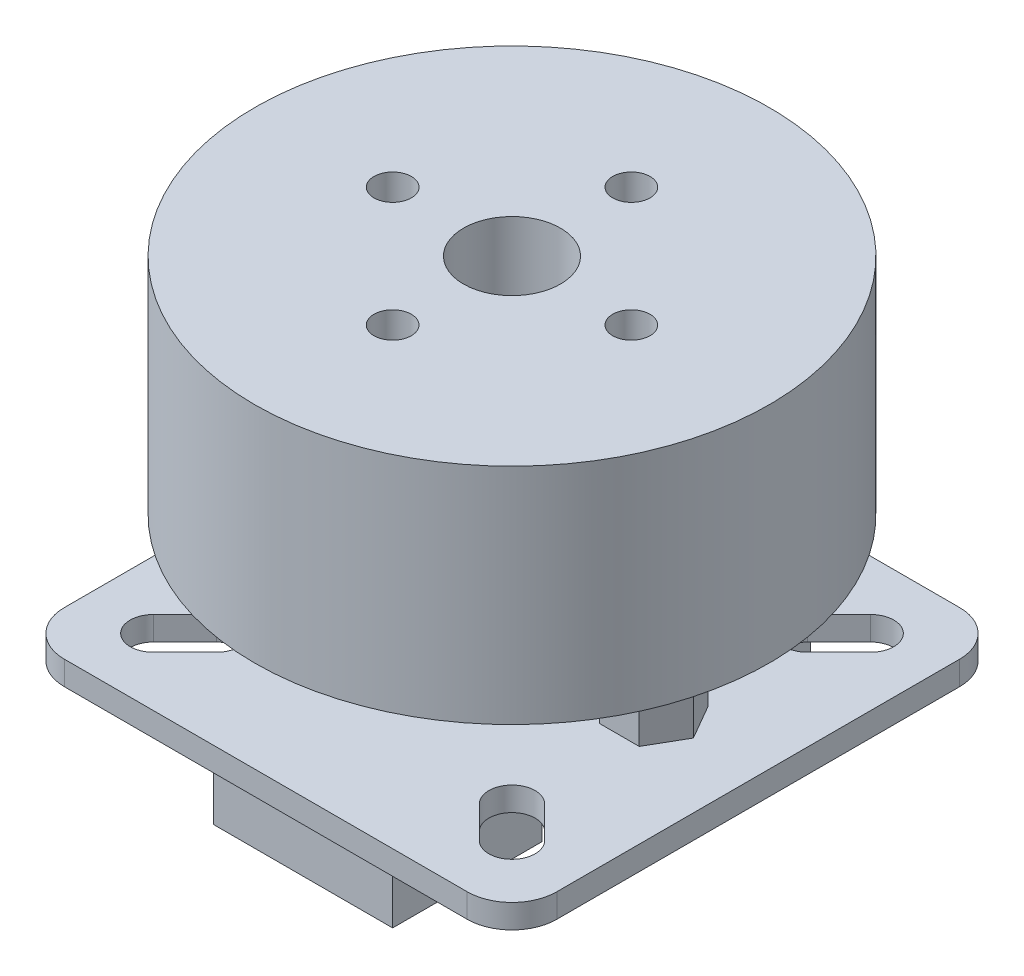
SolidWorks part; units mm, degrees
material "Cast Alloy Steel"
ref_plane "Front Plane" through (0, 0, 0) normal (0, 0, 1) x (1, 0, 0)
ref_plane "Top Plane" through (0, 0, 0) normal (0, 1, 0) x (1, 0, 0)
ref_plane "Right Plane" through (0, 0, 0) normal (1, 0, 0) x (0, 0, -1)
sketch "Sketch1" plane through (0, 0, 0) normal (0, 1, 0) x (1, 0, 0)
  circle A0 centre (0, 0) radius 17.25
  dimension "D1" = 34.5
extrude "Boss-Extrude1" add sketch "Sketch1" along normal blind 15
sketch "Sketch2" plane through (0, 0, 0) normal (0, -1, 0) x (1, 0, 0)
  circle A0 centre (0, 0) radius 6
  dimension "D1" = 12
extrude "Boss-Extrude2" add sketch "Sketch2" along normal blind 4.5
sketch "Sketch3" plane through (0, 0, 0) normal (0, -1, 0) x (1, 0, 0)
  line L1 (-6.8442, 0) -> (-8.1721, 2.3)
  line L2 (-8.1721, 2.3) -> (-10.8279, 2.3)
  line L3 (-10.8279, 2.3) -> (-12.1558, 0)
  line L4 (-12.1558, 0) -> (-10.8279, -2.3)
  line L5 (-10.8279, -2.3) -> (-8.1721, -2.3)
  line L6 (-8.1721, -2.3) -> (-6.8442, 0)
  line L7 (12.1558, 0) -> (10.8279, 2.3)
  line L8 (10.8279, 2.3) -> (8.1721, 2.3)
  line L9 (8.1721, 2.3) -> (6.8442, 0)
  line L10 (6.8442, 0) -> (8.1721, -2.3)
  line L11 (8.1721, -2.3) -> (10.8279, -2.3)
  line L12 (10.8279, -2.3) -> (12.1558, 0)
  circle A0 centre (0, 0) radius 9.5 construction
  circle A1 centre (-9.5, 0) radius 2.3 construction
  circle A2 centre (9.5, 0) radius 2.3 construction
  dimension "D1" = 19
  dimension "D2" = 4.6
  dimension "D3" = 4.6
extrude "Boss-Extrude3" add sketch "Sketch3" along normal blind 6.9
sketch "Sketch4" plane through (0, -6.9, 0) normal (0, -1, 0) x (1, 0, 0)
  line L0 (0, 21.6331) -> (0, -20.544) construction
  line L1 (-16.5, -16.5) -> (-16.5, 16.5)
  line L2 (-16.5, -16.5) -> (16.5, -16.5)
  line L3 (16.5, -16.5) -> (16.5, 16.5)
  line L4 (-16.5, 16.5) -> (16.5, 16.5)
  line L5 (24.0911, 0) -> (-31.8412, 0) construction
  line L6 (-13.1168, -10.9248) -> (-10.9955, -8.8035)
  line L7 (-10.9248, -13.1168) -> (-8.8035, -10.9955)
  line L8 (-13.1168, 10.9248) -> (-10.9955, 8.8035)
  line L9 (-10.9248, 13.1168) -> (-8.8035, 10.9955)
  line L10 (13.1168, -10.9248) -> (10.9955, -8.8035)
  line L11 (10.9248, -13.1168) -> (8.8035, -10.9955)
  line L12 (13.1168, 10.9248) -> (10.9955, 8.8035)
  line L13 (10.9248, 13.1168) -> (8.8035, 10.9955)
  circle A0 centre (0, 0) radius 17 construction
  circle A1 centre (0, 0) radius 14 construction
  circle A2 centre (0, 0) radius 9.5 construction
  circle A3 centre (0, 0) radius 8 construction
  arc A6 (-13.1168, -10.9248) -> (-10.9248, -13.1168) centre (-12.0208, -12.0208) ccw
  arc A13 (-13.1168, 10.9248) -> (-10.9248, 13.1168) centre (-12.0208, 12.0208) cw
  arc A14 (-8.8035, -10.9955) -> (-10.9955, -8.8035) centre (-9.8995, -9.8995) ccw
  arc A15 (-8.8035, 10.9955) -> (-10.9955, 8.8035) centre (-9.8995, 9.8995) cw
  arc A16 (13.1168, -10.9248) -> (10.9248, -13.1168) centre (12.0208, -12.0208) cw
  arc A17 (8.8035, -10.9955) -> (10.9955, -8.8035) centre (9.8995, -9.8995) cw
  arc A18 (8.8035, 10.9955) -> (10.9955, 8.8035) centre (9.8995, 9.8995) ccw
  arc A19 (13.1168, 10.9248) -> (10.9248, 13.1168) centre (12.0208, 12.0208) ccw
  dimension "D2" = 34
  dimension "D3" = 28
  dimension "D4" = 19
  dimension "D5" = 16
  dimension "D10" = 1.55
  dimension "D11" = 1.55
  dimension "D1" = 33
extrude "Boss-Extrude4" add sketch "Sketch4" along normal blind 1.6
fillet "Fillet1" radius 3 4 edges at (-16.5, -7.7, 16.5) (16.5, -7.7, 16.5) (16.5, -7.7, -16.5) (-16.5, -7.7, -16.5)
sketch "Sketch5" plane through (0, -8.5, 0) normal (0, -1, 0) x (1, 0, 0)
  line L0 (-23.8077, 0) -> (24.343, 0) construction
  line L1 (9.365, -12.0208) -> (10.6929, -14.3208)
  line L2 (10.6929, -14.3208) -> (13.3487, -14.3208)
  line L3 (13.3487, -14.3208) -> (14.6766, -12.0208)
  line L4 (14.6766, -12.0208) -> (13.3487, -9.7208)
  line L5 (13.3487, -9.7208) -> (10.6929, -9.7208)
  line L6 (10.6929, -9.7208) -> (9.365, -12.0208)
  line L7 (0, 21.4722) -> (0, -22.5606) construction
  line L8 (-10.6929, -9.7208) -> (-9.365, -12.0208)
  line L9 (-13.3487, -9.7208) -> (-10.6929, -9.7208)
  line L10 (-14.6766, -12.0208) -> (-13.3487, -9.7208)
  line L11 (-13.3487, -14.3208) -> (-14.6766, -12.0208)
  line L12 (-10.6929, -14.3208) -> (-13.3487, -14.3208)
  line L13 (-9.365, -12.0208) -> (-10.6929, -14.3208)
  line L14 (-13.3487, 14.3208) -> (-14.6766, 12.0208)
  line L15 (-14.6766, 12.0208) -> (-13.3487, 9.7208)
  line L16 (-13.3487, 9.7208) -> (-10.6929, 9.7208)
  line L17 (-10.6929, 9.7208) -> (-9.365, 12.0208)
  line L18 (-9.365, 12.0208) -> (-10.6929, 14.3208)
  line L19 (-10.6929, 14.3208) -> (-13.3487, 14.3208)
  line L20 (10.6929, 9.7208) -> (9.365, 12.0208)
  line L21 (13.3487, 9.7208) -> (10.6929, 9.7208)
  line L22 (14.6766, 12.0208) -> (13.3487, 9.7208)
  line L23 (13.3487, 14.3208) -> (14.6766, 12.0208)
  line L24 (10.6929, 14.3208) -> (13.3487, 14.3208)
  line L25 (9.365, 12.0208) -> (10.6929, 14.3208)
  circle A0 centre (12.0208, -12.0208) radius 2.3 construction
  circle A1 centre (12.0208, -12.0208) radius 1.25
  circle A2 centre (-12.0208, -12.0208) radius 1.25
  circle A3 centre (-12.0208, 12.0208) radius 1.25
  circle A4 centre (12.0208, 12.0208) radius 1.25
  dimension "D2" = 2.5
  dimension "D1" = 4.6
sketch "Sketch9" plane through (0, -8.5, 0) normal (0, -1, 0) x (1, 0, 0)
  line L0 (0, 4) -> (0, -4) construction
  line L1 (-6, 14) -> (6, 14)
  line L2 (-6, 14) -> (-6, 4)
  line L3 (-6, 4) -> (6, 4)
  line L4 (6, 14) -> (6, 4)
  line L5 (-6, -4) -> (6, -4)
  line L6 (-6, -4) -> (-6, -14)
  line L7 (-6, -14) -> (6, -14)
  line L8 (6, -4) -> (6, -14)
  point P8 (0, -4)
  point P10 (0, 4)
  point P13 (0, 0)
  dimension "D1" = 10
  dimension "D2" = 12
  dimension "D3" = 8
extrude "Boss-Extrude6" add sketch "Sketch9" along normal blind 5.5
sketch "Sketch10" plane through (0, 15, 0) normal (0, 1, 0) x (1, 0, 0)
  circle A0 centre (0, 0) radius 8 construction
  circle A1 centre (0, 8) radius 1.25
  circle A2 centre (8, 0) radius 1.25
  circle A3 centre (0, -8) radius 1.25
  circle A4 centre (-8, 0) radius 1.25
  dimension "D1" = 16
  dimension "D2" = 2.5
extrude "Cut-Extrude1" cut sketch "Sketch10" against normal blind 4
sketch "Sketch11" plane through (0, -8.5, 0) normal (0, -1, 0) x (1, 0, 0)
  circle A0 centre (-9.5, 0) radius 3.1
  circle A1 centre (9.5, 0) radius 3.1
  dimension "D1" = 6.2
extrude "Boss-Extrude7" add sketch "Sketch11" along normal blind 1.4
fillet "Fillet2" radius 2 2 edges at (9.5, -9.9, -3.1) (-9.5, -9.9, -3.1)
sketch "Sketch12" plane through (0, 15, 0) normal (0, 1, 0) x (1, 0, 0)
  circle A0 centre (0, 0) radius 3.25
  dimension "D1" = 6.5
extrude "Cut-Extrude2" cut sketch "Sketch12" against normal blind 12
